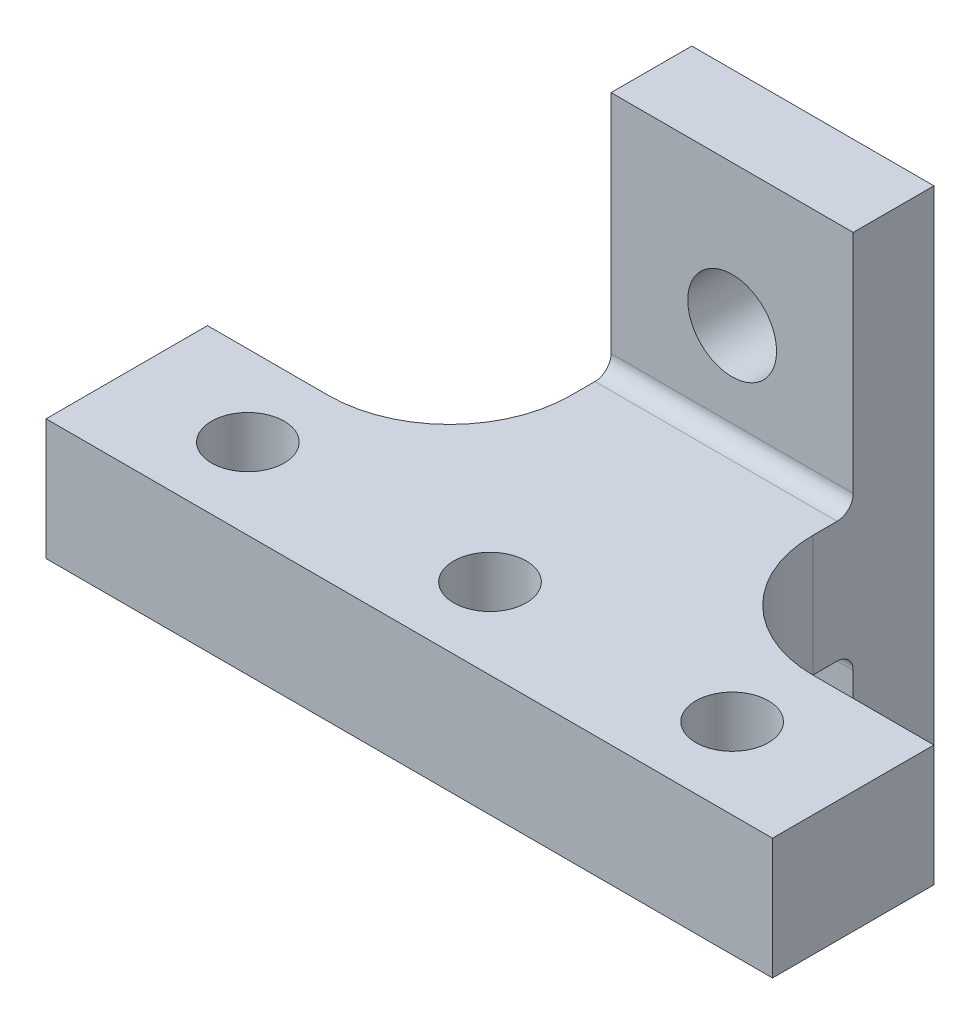
SolidWorks part; units mm, degrees
ref_plane "前视基准面" through (0, 0, 0) normal (0, 0, 1) x (1, 0, 0)
ref_plane "上视基准面" through (0, 0, 0) normal (0, 1, 0) x (1, 0, 0)
ref_plane "右视基准面" through (0, 0, 0) normal (1, 0, 0) x (0, 0, -1)
sketch "草图1" plane through (0, 0, 0) normal (0, 0, 1) x (1, 0, 0)
  line L0 (0, 0) -> (0, 20) construction
  line L1 (-15, -37.5) -> (15, -37.5)
  line L2 (-15, -37.5) -> (-15, 37.5)
  line L3 (-15, 37.5) -> (15, 37.5)
  line L4 (15, -37.5) -> (15, 37.5)
  line L5 (-15, -37.5) -> (15, 37.5) construction
  line L6 (-15, 37.5) -> (15, -37.5) construction
  line L7 (0, 0) -> (0, -20) construction
  circle A0 centre (0, 20) radius 5.5
  circle A1 centre (0, -20) radius 5.5
  point P0 (0, 0)
  dimension "D3" = 11
  dimension "D4" = 11
  dimension "D1" = 30
  dimension "D2" = 75
extrude "凸台-拉伸1" add sketch "草图1" along normal blind 10
sketch "草图2" plane through (0, 0, 10) normal (0, 0, 1) x (1, 0, 0)
  line L0 (15, -37.5) -> (15, 37.5) construction
  line L1 (-15, 7.5) -> (15, 7.5)
  line L2 (-15, 7.5) -> (-15, -7.5)
  line L3 (-15, -7.5) -> (15, -7.5)
  line L4 (15, 7.5) -> (15, -7.5)
  line L5 (-15, 7.5) -> (15, -7.5) construction
  line L6 (-15, -7.5) -> (15, 7.5) construction
  point P0 (0, 0)
  dimension "D1" = 15
extrude "凸台-拉伸2" add sketch "草图2" along normal blind 40
fillet "圆角1" radius 2 2 edges at (0, 7.5, 10) (0, -7.5, 10)
sketch "草图3" plane through (0, -7.5, 0) normal (0, -1, 0) x (-1, 0, 0)
  line L0 (0, -10) -> (0, -40) construction
  line L1 (-15, -10) -> (15, -10) construction
  circle A0 centre (0, -40) radius 4.5
extrude "切除-拉伸1" cut sketch "草图3" against normal up to vertex (15 mm away) up to point (15, 7.5, 50)
sketch "草图5" plane through (15, 0, 0) normal (1, 0, 0) x (0, 0, -1)
  line L0 (-50, 7.5) -> (-12, 7.5) construction
  line L1 (-50, -7.5) -> (-30, -7.5)
  line L2 (-50, -7.5) -> (-50, 7.5)
  line L3 (-50, 7.5) -> (-30, 7.5)
  line L4 (-30, -7.5) -> (-30, 7.5)
  line L5 (-40, 7.5) -> (-40, -7.5) construction
  line L6 (-50, 0) -> (-30, 0) construction
  point P64 (-40, 0)
extrude "凸台-拉伸3" add sketch "草图5" along normal blind 30
sketch "草图6" plane through (0, -7.5, 0) normal (0, -1, 0) x (-1, 0, 0)
  line L0 (0, -40) -> (-30, -40) construction
  circle A0 centre (-30, -40) radius 4.5
extrude "切除-拉伸2" cut sketch "草图6" against normal blind 30
fillet "圆角2" radius 15 1 edges at (15, 0, 30)
sketch "草图7" plane through (-15, 0, 0) normal (-1, 0, 0) x (0, 0, 1)
  line L0 (50, -7.5) -> (12, -7.5) construction
  line L1 (50, 7.5) -> (30, 7.5)
  line L2 (50, 7.5) -> (50, -7.5)
  line L3 (50, -7.5) -> (30, -7.5)
  line L4 (30, 7.5) -> (30, -7.5)
  line L5 (40, -7.5) -> (40, 7.5) construction
  line L6 (50, 0) -> (30, 0) construction
  point P88 (40, 0)
extrude "凸台-拉伸4" add sketch "草图7" along normal blind 30
fillet "圆角3" radius 15 1 edges at (-15, 0, 30)
sketch "草图8" plane through (0, -7.5, 0) normal (0, -1, 0) x (-1, 0, 0)
  line L0 (0, -40) -> (30, -40) construction
  circle A0 centre (30, -40) radius 4.5
extrude "切除-拉伸3" cut sketch "草图8" against normal blind 30
